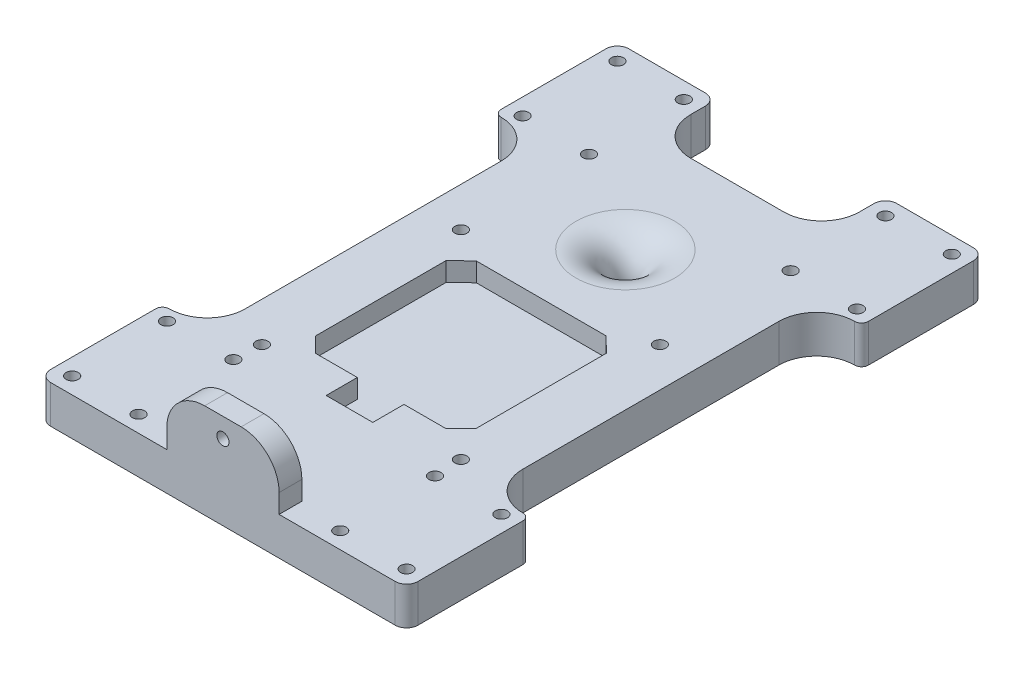
SolidWorks part; units mm, degrees
ref_plane "Front Plane" through (0, 0, 0) normal (0, 0, 1) x (1, 0, 0)
ref_plane "Top Plane" through (0, 0, 0) normal (0, 1, 0) x (1, 0, 0)
ref_plane "Right Plane" through (0, 0, 0) normal (1, 0, 0) x (0, 0, -1)
sketch "Sketch1" plane through (0, 0, 0) normal (0, 1, 0) x (1, 0, 0)
  line L0 (1.3315, -24.9796) -> (22.4815, -24.9796) construction
  line L1 (-10.9185, 58.7521) -> (13.5815, 58.7521)
  line L2 (-35.2778, 33.1128) -> (-35.2778, -34.3872)
  line L4 (37.9413, 33.1128) -> (37.9413, -34.3872)
  line L5 (-35.2778, 58.7521) -> (35.2778, -58.7521) construction
  line L6 (-35.2778, -58.7521) -> (35.2778, 58.7521) construction
  line L13 (-42.7559, 71.2502) -> (-25.2559, 71.2502)
  line L14 (-42.7559, 71.2502) -> (-42.7559, 46.2502)
  line L15 (-42.7559, 46.2502) -> (-25.2559, 46.2502)
  line L16 (-25.2559, 71.2502) -> (-25.2559, 46.2502)
  line L17 (-42.7559, 71.2502) -> (-25.2559, 46.2502) construction
  line L18 (-42.7559, 46.2502) -> (-25.2559, 71.2502) construction
  line L29 (37.9413, -0.6372) -> (-35.2778, -0.6372) construction
  line L31 (-19.8185, 7.0314) -> (22.4815, 7.0314)
  line L32 (-19.8185, 7.0314) -> (-19.8185, -35.2686)
  line L33 (-19.8185, -35.2686) -> (22.4815, -35.2686)
  line L34 (22.4815, 7.0314) -> (22.4815, -35.2686)
  line L35 (1.3315, -24.9796) -> (-19.8185, -24.9796) construction
  line L36 (1.3315, -61.047) -> (1.3315, 58.7521) construction
  line L44 (-34.0059, 71.2502) -> (-34.0059, 75.5875) construction
  line L45 (-45.2932, 43.1128) -> (-45.2778, 43.1128)
  line L46 (-47.0932, 44.9128) -> (-47.0932, 72.5875)
  line L47 (-44.0932, 75.5875) -> (-23.9185, 75.5875)
  line L48 (-20.9185, 68.7521) -> (-20.9185, 72.5875)
  line L49 (-47.0932, 43.1128) -> (-20.9185, 75.5875) construction
  line L50 (-47.0932, 75.5875) -> (-23.4634, 43.9577) construction
  line L51 (-42.7559, 58.7502) -> (-47.0932, 58.7502) construction
  line L52 (45.4189, 46.2502) -> (27.9189, 46.2502)
  line L53 (27.9189, 71.2502) -> (27.9189, 46.2502)
  line L54 (45.4189, 71.2502) -> (27.9189, 71.2502)
  line L55 (45.4189, 71.2502) -> (45.4189, 46.2502)
  line L56 (46.7562, 75.5875) -> (26.5815, 75.5875)
  line L57 (23.5815, 68.7521) -> (23.5815, 72.5875)
  line L58 (47.9562, 43.1128) -> (47.9413, 43.1128)
  line L59 (49.7562, 44.9128) -> (49.7562, 72.5875)
  line L60 (49.7562, -46.1872) -> (49.7562, -73.8619)
  line L61 (47.9562, -44.3872) -> (47.9413, -44.3872)
  line L63 (46.7562, -76.8619) -> (26.5815, -76.8619)
  line L64 (45.4189, -72.5246) -> (45.4189, -47.5246)
  line L65 (45.4189, -72.5246) -> (27.9189, -72.5246)
  line L66 (27.9189, -72.5246) -> (27.9189, -47.5246)
  line L67 (45.4189, -47.5246) -> (27.9189, -47.5246)
  line L68 (-44.0932, -76.8619) -> (-23.9185, -76.8619)
  line L70 (-45.2932, -44.3872) -> (-45.2778, -44.3872)
  line L71 (-47.0932, -46.1872) -> (-47.0932, -73.8619)
  line L72 (-42.7559, -47.5246) -> (-25.2559, -47.5246)
  line L73 (-25.2559, -72.5246) -> (-25.2559, -47.5246)
  line L74 (-42.7559, -72.5246) -> (-25.2559, -72.5246)
  line L75 (-42.7559, -72.5246) -> (-42.7559, -47.5246)
  line L76 (22.4815, 3.1566) -> (18.4091, 7.0314)
  line L77 (-15.8437, -35.2686) -> (-19.8185, -31.2938)
  line L79 (-19.8185, 3.1566) -> (-15.7461, 7.0314)
  line L80 (18.5067, -35.2686) -> (22.4815, -31.2938)
  line L81 (-4.8199, -35.2686) -> (-4.8199, -43.4965)
  line L82 (-4.8199, -43.4965) -> (7.4829, -43.4965)
  line L83 (7.4829, -43.4965) -> (7.4829, -35.2686)
  line L84 (-23.9185, -76.8619) -> (26.5815, -76.8619)
  circle A0 centre (1.3315, 29.2618) radius 3
  circle A1 centre (-25.2559, 71.2502) radius 1.6
  circle A2 centre (-42.7559, 71.2502) radius 1.6
  circle A3 centre (-42.7559, 46.2502) radius 1.6
  circle A4 centre (-25.2559, 46.2502) radius 1.6
  circle A5 centre (27.9189, 46.2502) radius 1.6
  circle A6 centre (45.4189, 46.2502) radius 1.6
  circle A7 centre (45.4189, 71.2502) radius 1.6
  circle A8 centre (27.9189, 71.2502) radius 1.6
  circle A9 centre (45.4189, -47.5246) radius 1.6
  circle A10 centre (27.9189, -47.5246) radius 1.6
  circle A11 centre (27.9189, -72.5246) radius 1.6
  circle A12 centre (45.4189, -72.5246) radius 1.6
  circle A13 centre (-25.2559, -47.5246) radius 1.6
  circle A14 centre (-42.7559, -47.5246) radius 1.6
  circle A15 centre (-42.7559, -72.5246) radius 1.6
  circle A16 centre (-25.2559, -72.5246) radius 1.6
  arc A18 (37.9413, -34.3872) -> (47.9413, -44.3872) centre (47.9413, -34.3872) ccw
  arc A19 (37.9413, 33.1128) -> (47.9413, 43.1128) centre (47.9413, 33.1128) cw
  arc A20 (13.5815, 58.7521) -> (23.5815, 68.7521) centre (13.5815, 68.7521) ccw
  arc A21 (-10.9185, 58.7521) -> (-20.9185, 68.7521) centre (-10.9185, 68.7521) cw
  arc A22 (-45.2778, 43.1128) -> (-35.2778, 33.1128) centre (-45.2778, 33.1128) cw
  arc A23 (-35.2778, -34.3872) -> (-45.2778, -44.3872) centre (-45.2778, -34.3872) cw
  arc A25 (-47.0932, 72.5875) -> (-44.0932, 75.5875) centre (-44.0932, 72.5875) cw
  arc A26 (-23.9185, 75.5875) -> (-20.9185, 72.5875) centre (-23.9185, 72.5875) cw
  arc A27 (26.5815, 75.5875) -> (23.5815, 72.5875) centre (26.5815, 72.5875) ccw
  arc A28 (46.7562, 75.5875) -> (49.7562, 72.5875) centre (46.7562, 72.5875) cw
  arc A29 (49.7562, -73.8619) -> (46.7562, -76.8619) centre (46.7562, -73.8619) cw
  arc A32 (-44.0932, -76.8619) -> (-47.0932, -73.8619) centre (-44.0932, -73.8619) cw
  arc A33 (47.9562, 43.1128) -> (49.7562, 44.9128) centre (47.9562, 44.9128) ccw
  arc A34 (49.7562, -46.1872) -> (47.9562, -44.3872) centre (47.9562, -46.1872) ccw
  arc A35 (-45.2932, -44.3872) -> (-47.0932, -46.1872) centre (-45.2932, -46.1872) ccw
  arc A36 (-45.2932, 43.1128) -> (-47.0932, 44.9128) centre (-45.2932, 44.9128) cw
  point P0 (0, 0)
  point P22 (1.3315, -14.7624)
  point P101 (23.5815, 75.5875)
  point P104 (49.7562, 75.5875)
  point P107 (49.7562, -76.8619)
  point P110 (23.5815, -76.8619)
  point P113 (-20.9185, -76.8619)
  point P116 (-47.0932, -76.8619)
  point P119 (49.7562, 43.1128)
  point P122 (49.7562, -44.3872)
  point P125 (-47.0932, -44.3872)
  point P143 (1.3315, -43.4965)
  dimension "D2" = 25
  dimension "D5" = 3
  dimension "D6" = 1.8
  dimension "D3" = 17.5
  dimension "D7" = 42.3
  dimension "D8" = 45
  dimension "D9" = 67.5
  dimension "D10" = 24.5
extrude "Boss-Extrude1" add sketch "Sketch1" along normal blind 10 contours L33 L80 L34 L76 L31 L79 L32 L77 | L82 L83 L33 L81 | L63 L84 L68 A32 L71 A35 L70 A23 L2 A22 L45 A36 L46 A25 L47 A26 L48 A21 L1 A20 L57 A27 L56 A28 L59 A33 L58 A19 L4 A18 L61 A34 L60 A29 | A13 | A16 | A15 | A14 | A11 | A12 | A9 | A10 | A1 | A4 | A3 | A2 | A5 | A6 | A7 | A8 | A0 region at (1.3315, 0, 14.1187) region at (1.3315, 0, 39.3825)
extrude "Boss-Extrude2" add sketch "Sketch1<3>" along normal blind 5 contours L82 L83 L33 L81 | L32 L31 L34 L33 region at (1.3315, 0, 39.3825)
sketch "Sketch1<3>" plane through (0, 0, 0) normal (0, 1, 0) x (1, 0, 0) same geometry as "Sketch1"
sketch "Sketch3" plane through (0, 10, 0) normal (0, 1, 0) x (1, 0, 0)
  line L0 (22.4815, 3.1566) -> (22.4815, -31.2938) construction
  line L1 (-19.8185, -35.2686) -> (22.4815, -35.2686) construction
  line L2 (-19.8185, -35.2686) -> (-19.8185, 7.0314) construction
  line L3 (-19.8185, 7.0314) -> (22.4815, 7.0314) construction
  line L4 (22.4815, -35.2686) -> (22.4815, 7.0314) construction
  line L5 (-19.8185, 3.1566) -> (-19.8185, -31.2938) construction
  line L6 (-15.7461, 7.0314) -> (18.4091, 7.0314) construction
  line L7 (-15.8437, -35.2686) -> (-4.8199, -35.2686) construction
  line L8 (-17.8311, -33.2812) -> (-24.9022, -40.3523) construction
  line L9 (-15.8437, -35.2686) -> (-19.8185, -31.2938) construction
  line L10 (-19.8185, -14.1186) -> (22.4815, -14.1186) construction
  line L11 (1.3315, 7.0314) -> (1.3315, -35.2686) construction
  circle A4 centre (-24.9022, -40.3523) radius 1.6
  circle A5 centre (27.5652, -40.3523) radius 1.6
  circle A6 centre (27.5652, 12.1151) radius 1.6
  circle A7 centre (-24.9022, 12.1151) radius 1.6
extrude "Cut-Extrude2" cut sketch "Sketch3" against normal blind 24
fillet "Fillet1" radius 10 1 edges at (1.3315, 10, -26.2618)
sketch "Sketch4" plane through (0, 10, 0) normal (0, 1, 0) x (1, 0, 0)
  line L0 (1.3315, 7.0314) -> (1.3315, -76.8619) construction
  line L5 (-15.7461, 7.0314) -> (18.4091, 7.0314) construction
  line L6 (46.7562, -76.8619) -> (-44.0932, -76.8619) construction
  line L12 (-13.4758, -70.8552) -> (16.1388, -70.8552)
  line L13 (-13.4758, -70.8552) -> (-13.4758, -76.8619)
  line L14 (-13.4758, -76.8619) -> (16.1388, -76.8619)
  line L15 (16.1388, -70.8552) -> (16.1388, -76.8619)
  line L16 (-13.4758, -70.8552) -> (16.1388, -76.8619) construction
  line L17 (-13.4758, -76.8619) -> (16.1388, -70.8552) construction
  point P6 (1.3315, -73.8585)
extrude "Boss-Extrude3" add sketch "Sketch4" along normal blind 15 contours L13 L12 L15 L14
fillet "Fillet2" radius 10 2 edges at (-13.4758, 25, 73.8585) (16.1388, 25, 73.8585)
sketch "Sketch5" plane through (0, 0, 76.8619) normal (0, 0, 1) x (1, 0, 0)
  line L0 (1.3315, 25) -> (1.3315, 0) construction
  line L1 (-3.4758, 25) -> (6.1388, 25) construction
  line L2 (-44.0932, 0) -> (46.7562, 0) construction
  circle A0 centre (1.3315, 19.8551) radius 1.6
extrude "Cut-Extrude3" cut sketch "Sketch5" against normal blind 15
